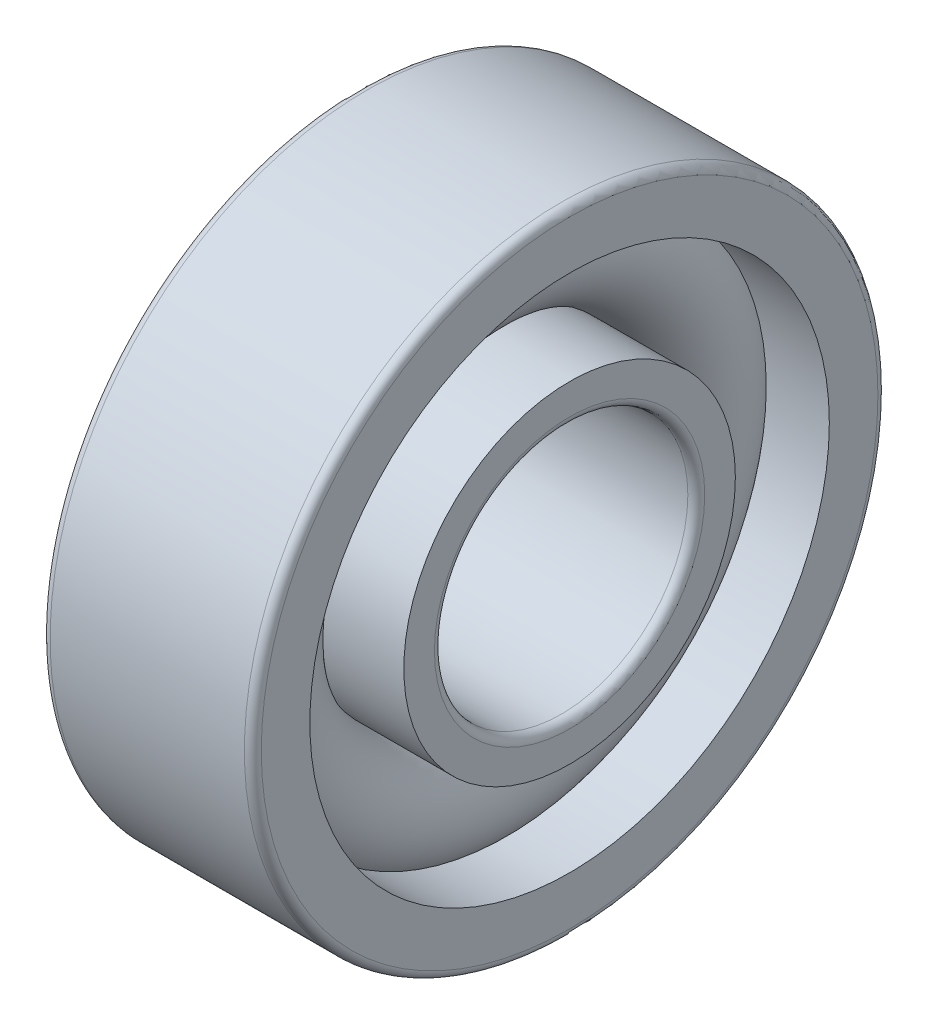
SolidWorks part; units mm, degrees
ref_plane "Plane1" through (0, 0, 0) normal (0, 0, 1) x (1, 0, 0)
ref_plane "Plane2" through (0, 0, 0) normal (0, 1, 0) x (1, 0, 0)
ref_plane "Plane3" through (0, 0, 0) normal (1, 0, 0) x (0, 0, -1)
sketch "Clipboard" plane through (0, 0, 0) normal (0, 0, 1) x (1, 0, 0)
  line L0 (-10, 0) -> (10, 0) construction
  line L1 (0, 0) -> (22.3471, -0.7804)
  line L2 (0, 0) -> (5.2468, 0.1832)
  line L3 (0, 0) -> (22.3471, -0.7804)
  line L4 (0, 0) -> (-22.3573, -0.3902)
  dimension "BallCLRad" = 5.25
sketch "CagSpiSke" plane through (0, 0, 0) normal (0, 0, 1) x (1, 0, 0)
  line L0 (0.3375, 5.025) -> (0.3375, 5.475)
  line L1 (0.3375, 5.475) -> (-0.3375, 5.475)
  line L2 (-0.3375, 5.475) -> (-0.3375, 5.025)
  line L3 (-0.3375, 5.025) -> (0.3375, 5.025)
  line L4 (-20.6375, 0) -> (20.6375, 0) construction
  line L5 (0, 0) -> (0, 23.7692) construction
  dimension "OD" = 10.95
  dimension "ID" = 10.05
revolve "CageSpine" add sketch "CagSpiSke" angle 0.001 about L4
ref_axis "Axis1" through (-50, 0, 0) along (1, 0, 0)
sketch "CagBalSke" plane through (0, 0, 0) normal (0, 0, 1) x (1, 0, 0)
  line L0 (-1.485, 5.25) -> (1.485, 5.25)
  line L1 (-1.905, 5.25) -> (1.905, 5.25) construction
  line L2 (-10, 0) -> (10, 0) construction
  line L3 (0, 0) -> (0, 24) construction
  arc A0 (1.485, 5.25) -> (-1.485, 5.25) centre (0, 5.25) cw
  dimension "BallCLRad" = 5.25
revolve "CageBall" [suppressed] add sketch "CagBalSke" angle 360 about L1 reverse direction yes
pattern_circular "CageBalls" [suppressed] count 2 every 180 about axis through (-50, 0, 0) along (1, 0, 0)
sketch "CagTrmODSke" plane through (0, 0, 0) normal (0, 0, 1) x (1, 0, 0)
  line L0 (1.486, 5.475) -> (1.486, 6.736)
  line L1 (1.486, 6.736) -> (-1.486, 6.736)
  line L2 (-1.486, 6.736) -> (-1.486, 5.475)
  line L3 (-1.486, 5.475) -> (1.486, 5.475)
  line L4 (-20.6375, 0) -> (20.6375, 0) construction
  line L5 (0, 0) -> (0, 25) construction
  dimension "Width" = 2.972
  dimension "ID" = 10.95
  dimension "OD" = 13.472
revolve "CageTrimOD" [suppressed] cut sketch "CagTrmODSke" angle 360 about L4 reverse direction yes
sketch "CagTrmIDSke" plane through (0, 0, 0) normal (0, 0, 1) x (1, 0, 0)
  line L0 (1.486, 3.766) -> (1.486, 5.025)
  line L1 (1.486, 5.025) -> (-1.486, 5.025)
  line L2 (-1.486, 5.025) -> (-1.486, 3.766)
  line L3 (-1.486, 3.766) -> (1.486, 3.766)
  line L4 (-20.6375, 0) -> (20.6375, 0) construction
  line L5 (0, 0) -> (0, 25) construction
  dimension "Width" = 2.972
  dimension "ID" = 7.532
  dimension "OD" = 10.05
revolve "CageTrimID" [suppressed] cut sketch "CagTrmIDSke" angle 360 about L4 reverse direction yes
sketch "BalSimSke" plane through (0, 0, 0) normal (0, 0, 1) x (1, 0, 0)
  line L0 (-10, 0) -> (10, 0) construction
  line L1 (-10, 5.25) -> (10, 5.25) construction
  line L2 (0, 0) -> (0, 23) construction
  circle A0 centre (0, 5.25) radius 1.35
  dimension "BallCLRad" = 5.25
  dimension "Ball_diameter" = 2.7
revolve "BallsSimplified" add sketch "BalSimSke" angle 360 about L0
sketch "BalDetSke" plane through (0, 0, 0) normal (0, 0, 1) x (1, 0, 0)
  line L0 (-1.35, 5.25) -> (1.35, 5.25)
  line L1 (-1.905, 5.25) -> (1.905, 5.25) construction
  line L2 (0, 0) -> (0, 25) construction
  arc A0 (1.35, 5.25) -> (-1.35, 5.25) centre (0, 5.25) cw
  dimension "BallCLRad" = 5.25
  dimension "Ball_diameter" = 2.7
revolve "BallDetailed" [suppressed] add sketch "BalDetSke" angle 360 about L1 reverse direction yes
sketch "InnRacSke" plane through (0, 0, 0) normal (0, 0, 1) x (1, 0, 0)
  line L0 (-0.9724, 4.35) -> (-2.5, 4.35)
  line L1 (-2.5, 4.35) -> (-2.5, 3.2)
  line L2 (-2.3, 3) -> (2.3, 3)
  line L3 (2.5, 3.2) -> (2.5, 3.925)
  line L4 (0, 3.925) -> (2.5, 3.925)
  line L5 (-20.6375, 0) -> (20.6375, 0) construction
  line L6 (0, 0) -> (0, 30) construction
  arc A0 (-2.5, 3.2) -> (-2.3, 3) centre (-2.3, 3.2) ccw
  arc A1 (2.3, 3) -> (2.5, 3.2) centre (2.3, 3.2) ccw
  arc A2 (0, 3.925) -> (-0.9724, 4.35) centre (0, 5.25) cw
  dimension "BallCLRad" = 5.25
  dimension "Fillet_radius" = 0.2
  dimension "Ball_diameter" = 2.65
  dimension "ID" = 6
  dimension "OD" = 8.7
  dimension "Width" = 5
revolve "InnerRace" add sketch "InnRacSke" angle 360 about L5 reverse direction yes
sketch "OutRacSke" plane through (0, 0, 0) normal (0, 0, 1) x (1, 0, 0)
  line L0 (0, 6.575) -> (-2.5, 6.575)
  line L1 (-2.5, 6.575) -> (-2.5, 7.3)
  line L2 (-2.3, 7.5) -> (2.3, 7.5)
  line L3 (2.5, 7.3) -> (2.5, 6.15)
  line L4 (2.5, 6.15) -> (0.9724, 6.15)
  line L5 (-20.6375, 0) -> (20.6375, 0) construction
  line L6 (0, 0) -> (0, 30) construction
  arc A0 (-2.5, 7.3) -> (-2.3, 7.5) centre (-2.3, 7.3) cw
  arc A1 (2.3, 7.5) -> (2.5, 7.3) centre (2.3, 7.3) cw
  arc A2 (0.9724, 6.15) -> (0, 6.575) centre (0, 5.25) ccw
  dimension "BallCLRad" = 5.25
  dimension "Fillet_radius" = 0.2
  dimension "Ball_diameter" = 2.65
  dimension "Width" = 5
revolve "OuterRace" add sketch "OutRacSke" angle 360 about L5 reverse direction yes
pattern_circular "BallsDetailed" [suppressed] count 2 every 180 about axis through (-50, 0, 0) along (1, 0, 0)
equation "\"BallCLRad@Clipboard\" = ( \"OD@OutRacSke\" + \"ID@InnRacSke\" ) / 4"
equation "\"BallCLRad@BalSimSke\" = \"BallCLRad@Clipboard\""
equation "\"BallCLRad@BalDetSke\" = \"BallCLRad@Clipboard\""
equation "\"BallCLRad@InnRacSke\" = \"BallCLRad@Clipboard\""
equation "\"BallCLRad@OutRacSke\" = \"BallCLRad@Clipboard\""
equation "\"Ball_diameter@InnRacSke\" = \"Ball_diameter@BalDetSke\" - 0.05"
equation "\"Ball_diameter@OutRacSke\" = \"Ball_diameter@BalDetSke\" - 0.05"
equation "\"Ball_diameter@BalSimSke\" = \"Ball_diameter@BalDetSke\""
equation "\"Width@OutRacSke\" = \"Width@InnRacSke\""
equation "\"Fillet_radius@OutRacSke\" = \"Fillet_radius@InnRacSke\""
equation "\"Max_count@Clipboard\" = int( 3.14159265 / atn(( \"Ball_diameter@BalDetSke\" / 2) / sqr( \"BallCLRad@Clipboard\"  *  \"BallCLRad@Clipboard\" - ( \"Ball_diameter@BalDetSke\" / 2) *  ( \"Ball_diameter@BalDetSke\" / 2))))"
equation "\"Max_count@Clipboard\" = ((sgn( \"Max_count@Clipboard\" - \"Count@Clipboard\" )-1)*( \"Max_count@Clipboard\" - \"Count@Clipboard\" ))/-2+ \"Count@Clipboard\""
equation "\"Count@BallsDetailed\" = int( \"Show_count@Clipboard\" ) "
equation "\"Count@BallsDetailed\" = ((sgn( \"Count@BallsDetailed\" - \"Max_count@Clipboard\" )-1)*( \"Count@BallsDetailed\" - \"Max_count@Clipboard\" ))/-2+ \"Max_count@Clipboard\""
equation "\"Count@BallsDetailed\" = ((sgn( \"Count@BallsDetailed\" - \"Min_count@Clipboard\" )+1)*( \"Count@BallsDetailed\" - \"Min_count@Clipboard\"))/2 +\"Min_count@Clipboard\""
equation "\"Angle@BallsDetailed\" = 360.0 / \"Max_count@Clipboard\""
equation "\"BallCLRad@CagBalSke\" = \"BallCLRad@Clipboard\""
equation "\"Count@CageBalls\" = \"Count@BallsDetailed\""
equation "\"Angle@CageBalls\" = \"Angle@BallsDetailed\""
equation "\"Angle@CageSpine\" =  \"Angle@CageBalls\" * ( \"Count@CageBalls\" -1 + int( \"Count@CageBalls\" / \"Max_count@Clipboard\" ) )  + 0.001 -  int( \"Count@CageBalls\" / \"Max_count@Clipboard\" ) * 0.001"
equation "\"Angle@CageSpine\" =  \"Angle@CageSpine\" * int( \"Min_count@Clipboard\" / 2) + int(1 / \"Min_count@Clipboard\")  * 0.001"
equation "\"CageWallOD@CagBalSke\" =  \"Ball_diameter@BalDetSke\" * 1.1"
equation "\"Thickness@CagSpiSke\" =  \"Ball_diameter@BalDetSke\" * 0.25"
equation "\"OD@CagTrmODSke\" = \"BallCLRad@Clipboard\" * 2 + \"CageWallOD@CagBalSke\" + 0.002"
equation "\"ID@CagTrmODSke\" = \"BallCLRad@Clipboard\" * 2 + \"Ball_diameter@BalDetSke\" / 6"
equation "\"OD@CagTrmIDSke\" = \"BallCLRad@Clipboard\" * 2 - \"Ball_diameter@BalDetSke\" / 6"
equation "\"ID@CagTrmIDSke\" = \"BallCLRad@Clipboard\" * 2 - \"CageWallOD@CagBalSke\" + 0.002"
equation "\"OD@CagSpiSke\" = \"ID@CagTrmODSke\""
equation "\"ID@CagSpiSke\" = \"OD@CagTrmIDSke\""
equation "\"Width@CagTrmODSke\" = \"CageWallOD@CagBalSke\" + 0.002"
equation "\"Width@CagTrmIDSke\" = \"CageWallOD@CagBalSke\" + 0.002"
